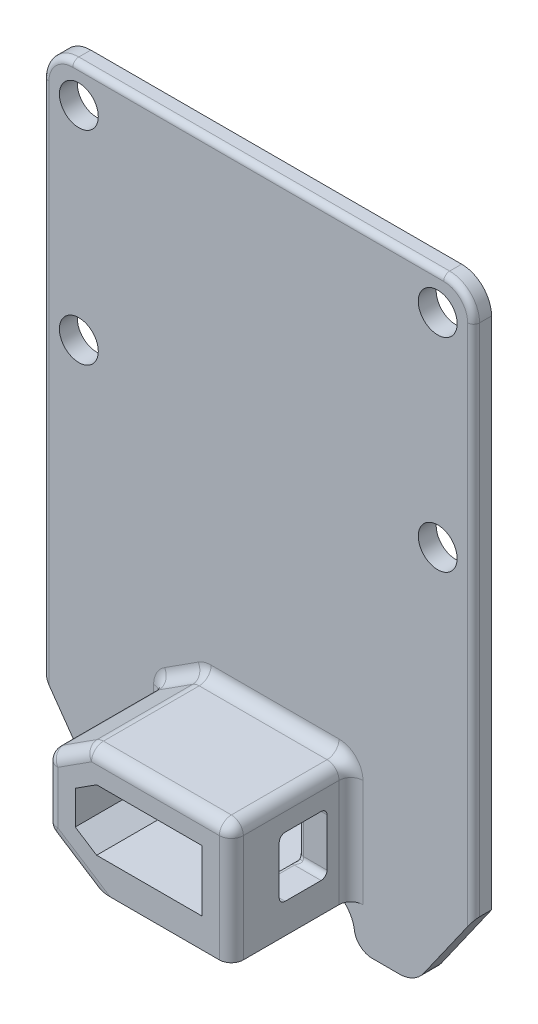
SolidWorks part; units mm, degrees
ref_plane "Plan de face" through (0, 0, 0) normal (0, 0, 1) x (1, 0, 0)
ref_plane "Plan de dessus" through (0, 0, 0) normal (0, 1, 0) x (1, 0, 0)
ref_plane "Plan de droite" through (0, 0, 0) normal (1, 0, 0) x (0, 0, -1)
sketch "Esquisse2" plane through (0, 0, 0) normal (0, 0, 1) x (1, 0, 0)
  line L0 (-11.0985, -98) -> (11.0985, -98)
  line L1 (31, 0) -> (-31, 0)
  line L4 (-36, -5) -> (-36, -91)
  line L12 (23.5481, -105) -> (19.0484, -105) construction
  line L13 (16.0975, -102.5406) -> (16.0166, -102.099) construction
  line L14 (-16.0975, -102.5406) -> (-16.0166, -102.099) construction
  line L15 (-23.5481, -105) -> (-19.0484, -105) construction
  line L18 (23.5481, -105) -> (19.0484, -105)
  line L19 (16.0975, -102.5406) -> (16.0166, -102.099)
  line L20 (-16.0975, -102.5406) -> (-16.0166, -102.099)
  line L21 (-23.5481, -105) -> (-19.0484, -105)
  line L29 (-27.6363, -102.8785) -> (-36, -91) construction
  line L30 (-27.6363, -102.8785) -> (-36, -91)
  line L31 (36, -91) -> (27.6363, -102.8785) construction
  line L32 (36, -91) -> (27.6363, -102.8785)
  line L33 (36, -91) -> (36, -5)
  circle A0 centre (30, -6) radius 3.25
  circle A1 centre (30, -40) radius 3.25
  circle A2 centre (-30, -40) radius 3.25
  circle A3 centre (-30, -6) radius 3.25
  arc A5 (16.0975, -102.5406) -> (19.0484, -105) centre (19.0484, -102) ccw construction
  arc A6 (16.0166, -102.099) -> (11.0985, -98) centre (11.0985, -103) ccw construction
  arc A7 (-11.0985, -98) -> (-16.0166, -102.099) centre (-11.0985, -103) ccw construction
  arc A8 (-19.0484, -105) -> (-16.0975, -102.5406) centre (-19.0484, -102) ccw construction
  arc A11 (16.0975, -102.5406) -> (19.0484, -105) centre (19.0484, -102) ccw
  arc A12 (16.0166, -102.099) -> (11.0985, -98) centre (11.0985, -103) ccw
  arc A13 (-11.0985, -98) -> (-16.0166, -102.099) centre (-11.0985, -103) ccw
  arc A14 (-19.0484, -105) -> (-16.0975, -102.5406) centre (-19.0484, -102) ccw
  arc A23 (23.5481, -105) -> (27.6363, -102.8785) centre (23.5481, -100) ccw construction
  arc A25 (23.5481, -105) -> (27.6363, -102.8785) centre (23.5481, -100) ccw
  arc A26 (-31, 0) -> (-36, -5) centre (-31, -5) ccw construction
  arc A28 (-31, 0) -> (-36, -5) centre (-31, -5) ccw
  arc A30 (-27.6363, -102.8785) -> (-23.5481, -105) centre (-23.5481, -100) ccw construction
  arc A31 (-27.6363, -102.8785) -> (-23.5481, -105) centre (-23.5481, -100) ccw
  arc A33 (36, -5) -> (31, 0) centre (31, -5) ccw construction
  arc A34 (36, -5) -> (31, 0) centre (31, -5) ccw
  point P4 (0, 0)
  dimension "D4" = 6.5
  dimension "D5" = 34
  dimension "D8" = 6
  dimension "D9" = 6
  dimension "D10" = 60
extrude "Boss.-Extru.1" add sketch "Esquisse2" along normal blind 3
sketch "Esquisse3" plane through (0, 0, 3) normal (0, 0, 1) x (1, 0, 0)
  line L0 (-7, -83) -> (10.5, -83) construction
  line L1 (10.5, -83) -> (10.5, -93) construction
  line L2 (10.5, -93) -> (-7, -93) construction
  line L3 (-7, -93) -> (-10.5, -90.75) construction
  line L4 (-10.5, -90.75) -> (-10.5, -85.25) construction
  line L5 (-10.5, -85.25) -> (-7, -83) construction
  line L6 (-10.5, -88) -> (10.5, -88) construction
  line L7 (-11.0985, -98) -> (11.0985, -98) construction
  line L8 (-7.0294, -82.9) -> (10.6, -82.9)
  line L9 (10.6, -82.9) -> (10.6, -93.1)
  line L10 (10.6, -93.1) -> (-7.0294, -93.1)
  line L11 (-7.0294, -93.1) -> (-10.6, -90.8046)
  line L12 (-10.6, -90.8046) -> (-10.6, -85.1954)
  line L13 (-10.6, -85.1954) -> (-7.0294, -82.9)
  point P9 (0, -88)
  point P12 (0, -98)
  dimension "D1" = 21
  dimension "D2" = 10
  dimension "D3" = 5.5
  dimension "D4" = 17.5
  dimension "D5" = 5
  dimension "D6" = 0.1
extrude "Enlèv. mat.-Extru.1" cut sketch "Esquisse3" against normal through all
sketch "Esquisse4" plane through (0, 0, 3) normal (0, 0, 1) x (1, 0, 0)
  line L18 (-10.6, -85.1954) -> (-10.6, -90.8046) construction
  line L19 (-10.6, -90.8046) -> (-7.0294, -93.1) construction
  line L20 (-7.0294, -93.1) -> (10.6, -93.1) construction
  line L21 (10.6, -93.1) -> (10.6, -82.9) construction
  line L22 (10.6, -82.9) -> (-7.0294, -82.9) construction
  line L23 (-7.0294, -82.9) -> (-10.6, -85.1954) construction
  line L24 (-10.6, -85.1954) -> (-10.6, -90.8046)
  line L25 (-10.6, -90.8046) -> (-7.0294, -93.1)
  line L26 (-7.0294, -93.1) -> (10.6, -93.1)
  line L27 (10.6, -93.1) -> (10.6, -82.9)
  line L28 (10.6, -82.9) -> (-7.0294, -82.9)
  line L29 (-7.0294, -82.9) -> (-10.6, -85.1954)
  line L30 (-8.4685, -78) -> (-15.5, -82.5202)
  line L31 (-15.5, -82.5202) -> (-15.5, -93.4798)
  line L32 (-15.5, -93.4798) -> (-8.4685, -98)
  line L33 (-8.4685, -98) -> (15.5, -98)
  line L34 (15.5, -98) -> (15.5, -78)
  line L35 (15.5, -78) -> (-8.4685, -78)
  dimension "D1" = 4.9
extrude "Boss.-Extru.2" add sketch "Esquisse4" along normal blind 20
sketch "Esquisse5" plane through (15.5, 0, 0) normal (1, 0, 0) x (0, 0, -1)
  line L0 (-23, -88) -> (-15, -88) construction
  line L2 (-23, -98) -> (-23, -78) construction
  line L3 (-15, -83) -> (-7, -83)
  line L4 (-15, -83) -> (-15, -93)
  line L5 (-15, -93) -> (-7, -93)
  line L6 (-7, -83) -> (-7, -93)
  point P2 (-23, -85)
  point P8 (-7, -88)
  dimension "D1" = 8
  dimension "D2" = 8
  dimension "D3" = 10
extrude "Enlèv. mat.-Extru.2" cut sketch "Esquisse5" against normal up to next
fillet "Congé2" radius 2 14 edges at (-11.9843, -95.7399, 3) (-15.5, -88, 3) (-11.9843, -80.2601, 3) (3.5157, -78, 3) (-11.9843, -95.7399, 23) (-11.9843, -80.2601, 23) (-15.5, -88, 23) (-15.5, -93.4798, 13) (-15.5, -82.5202, 13) (-8.4685, -78, 13) (15.5, -88, 3) (15.5, -78, 13) (15.5, -88, 23) (3.5157, -78, 23)
fillet "Congé3" radius 1 4 edges at (13.05, -93, 7) (13.05, -83, 15) (13.05, -93, 15) (13.05, -83, 7)
fillet "Congé4" radius 1 6 edges at (10.6, -83.2929, 7.2929) (10.6, -83.2929, 14.7071) (10.6, -88, 15) (10.6, -92.7071, 14.7071) (10.6, -92.7071, 7.2929) (10.6, -88, 7)
fillet "Fillet1" radius 1 5 edges at (-36, -48, 3) (0, 0, 3) (36, -48, 3) (-34.5355, -1.4645, 3) (34.5355, -1.4645, 3)
